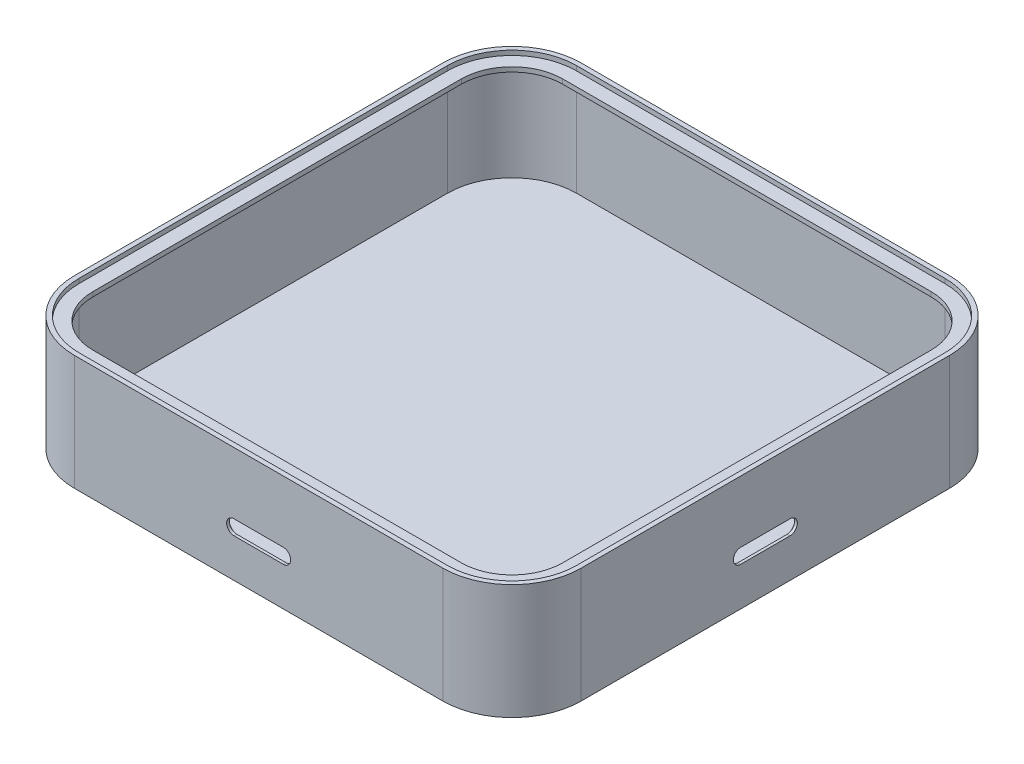
SolidWorks part; units mm, degrees
ref_plane "Front Plane" through (0, 0, 0) normal (0, 0, 1) x (1, 0, 0)
ref_plane "Top Plane" through (0, 0, 0) normal (0, 1, 0) x (1, 0, 0)
ref_plane "Right Plane" through (0, 0, 0) normal (1, 0, 0) x (0, 0, -1)
sketch "Sketch1" plane through (0, 0, 0) normal (0, 1, 0) x (1, 0, 0)
  line L1 (-80, -110) -> (80, -110)
  line L2 (-110, -80) -> (-110, 80)
  line L3 (-80, 110) -> (80, 110)
  line L4 (110, -80) -> (110, 80)
  line L5 (-110, -110) -> (110, 110) construction
  line L6 (-110, 110) -> (110, -110) construction
  arc A0 (-110, -80) -> (-80, -110) centre (-80, -80) ccw
  arc A1 (110, -80) -> (80, -110) centre (80, -80) cw
  arc A2 (110, 80) -> (80, 110) centre (80, 80) ccw
  arc A3 (-110, 80) -> (-80, 110) centre (-80, 80) cw
  point P0 (0, 0)
  dimension "D3" = 30
  dimension "D1" = 220
  dimension "D2" = 220
extrude "Boss-Extrude1" add sketch "Sketch1" along normal blind 50
shell "Shell1" thickness 2 removed face at (0, 50, 0)
sketch "Sketch5" plane through (110, 0, 0) normal (1, 0, 0) x (0, 0, -1)
  line L5 (-10.7, 20) -> (10.7, 20) construction
  line L6 (-10.7, 23.2) -> (10.7, 23.2)
  line L7 (-10.7, 16.8) -> (10.7, 16.8)
  line L9 (-110, 50) -> (-110, 0) construction
  line L10 (-10.7, 20) -> (10.7, 20) construction
  line L11 (-10.7, 24.2) -> (10.7, 24.2)
  line L12 (-10.7, 15.8) -> (10.7, 15.8)
  arc A4 (-10.7, 23.2) -> (-10.7, 16.8) centre (-10.7, 20) ccw
  arc A5 (10.7, 16.8) -> (10.7, 23.2) centre (10.7, 20) ccw
  arc A6 (-10.7, 24.2) -> (-10.7, 15.8) centre (-10.7, 20) ccw
  arc A7 (10.7, 15.8) -> (10.7, 24.2) centre (10.7, 20) ccw
  point P2 (0, 20)
  point P9 (-13.9, 20)
  point P10 (13.9, 20)
  point P13 (0, 20)
  dimension "D5" = 8.4
  dimension "D1" = 110
  dimension "D2" = 20
  dimension "D3" = 6.4
  dimension "D4" = 27.8
extrude "Cut-Extrude2" cut sketch "Sketch5" against normal blind 5 contours L7 A5 L6 A4 region at (110, 20, 0)
sketch "Sketch7" plane through (0, 0, 110) normal (0, 0, 1) x (1, 0, 0)
  line L0 (-10.7, 20) -> (10.7, 20) construction
  line L5 (-10.7, 23.2) -> (10.7, 23.2)
  line L6 (-10.7, 16.8) -> (10.7, 16.8)
  line L9 (-110, 50) -> (-110, 0) construction
  line L10 (-80, 0) -> (80, 0) construction
  line L11 (-10.7, 20) -> (10.7, 20) construction
  line L12 (-10.7, 24.2) -> (10.7, 24.2)
  line L13 (-10.7, 15.8) -> (10.7, 15.8)
  arc A4 (-10.7, 23.2) -> (-10.7, 16.8) centre (-10.7, 20) ccw
  arc A5 (10.7, 16.8) -> (10.7, 23.2) centre (10.7, 20) ccw
  arc A6 (-10.7, 24.2) -> (-10.7, 15.8) centre (-10.7, 20) ccw
  arc A7 (10.7, 15.8) -> (10.7, 24.2) centre (10.7, 20) ccw
  point P2 (0, 20)
  point P11 (0, 0)
  point P12 (-13.9, 20)
  point P13 (13.9, 20)
  point P16 (0, 20)
  dimension "D5" = 8.4
  dimension "D1" = 110
  dimension "D2" = 20
  dimension "D3" = 6.4
  dimension "D4" = 27.8
extrude "Cut-Extrude4" cut sketch "Sketch7" against normal blind 5 contours L6 A5 L5 A4 region at (0, 20, 110)
sketch "Sketch8" plane through (0, 2, 0) normal (0, 1, 0) x (1, 0, 0)
  line L16 (80, 108) -> (-80, 108)
  line L17 (-108, 80) -> (-108, -80)
  line L18 (-80, -108) -> (80, -108)
  line L19 (108, -80) -> (108, 80)
  line L20 (-102, 80) -> (-102, -80)
  line L21 (-80, -102) -> (80, -102)
  line L22 (102, -80) -> (102, 80)
  line L23 (80, 102) -> (-80, 102)
  line L24 (-102, 80) -> (-102, -80)
  line L25 (-80, -102) -> (80, -102)
  line L26 (102, -80) -> (102, 80)
  line L27 (80, 102) -> (-80, 102)
  arc A20 (-80, 108) -> (-108, 80) centre (-80, 80) ccw
  arc A21 (-108, -80) -> (-80, -108) centre (-80, -80) ccw
  arc A22 (80, -108) -> (108, -80) centre (80, -80) ccw
  arc A23 (108, 80) -> (80, 108) centre (80, 80) ccw
  arc A24 (-102, -80) -> (-80, -102) centre (-80, -80) ccw
  arc A25 (80, -102) -> (102, -80) centre (80, -80) ccw
  arc A26 (102, 80) -> (80, 102) centre (80, 80) ccw
  arc A27 (-80, 102) -> (-102, 80) centre (-80, 80) ccw
  arc A28 (-102, -80) -> (-80, -102) centre (-80, -80) ccw
  arc A29 (80, -102) -> (102, -80) centre (80, -80) ccw
  arc A30 (102, 80) -> (80, 102) centre (80, 80) ccw
  arc A31 (-80, 102) -> (-102, 80) centre (-80, 80) ccw
  dimension "D1" = 6
  dimension "D2" = 6
extrude "Boss-Extrude3" add sketch "Sketch8" along normal blind 2 from offset 44
extrude "Cut-Extrude6" cut sketch "Sketch5<5>" against normal up to next from offset 1.2 offset against normal yes
sketch "Sketch5<5>" plane through (110, 0, 0) normal (1, 0, 0) x (0, 0, -1) same geometry as "Sketch5"
extrude "Cut-Extrude7" cut sketch "Sketch7<3>" against normal up to next from offset 1.2 offset against normal yes
sketch "Sketch7<3>" plane through (0, 0, 110) normal (0, 0, 1) x (1, 0, 0) same geometry as "Sketch7"
